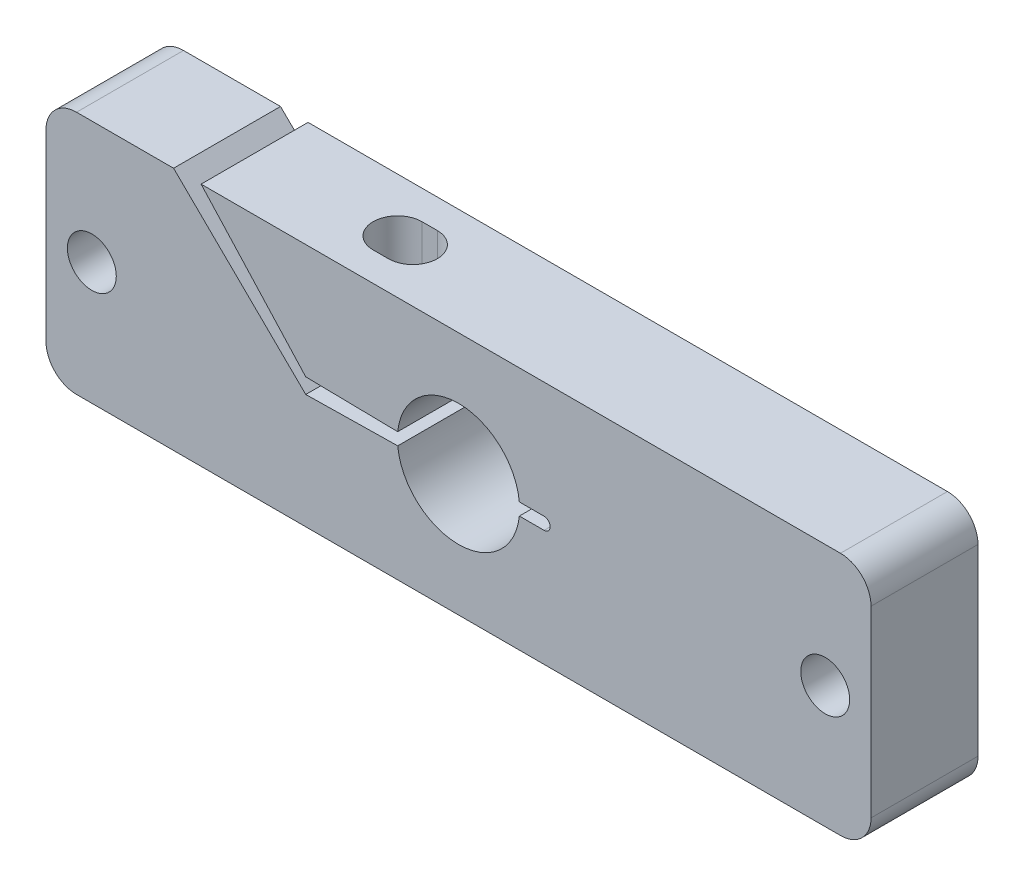
SolidWorks part; units mm, degrees
ref_plane "Front Plane" through (0, 0, 0) normal (0, 0, 1) x (1, 0, 0)
ref_plane "Top Plane" through (0, 0, 0) normal (0, 1, 0) x (1, 0, 0)
ref_plane "Right Plane" through (0, 0, 0) normal (1, 0, 0) x (0, 0, -1)
sketch "Sketch1" plane through (0, 0, 0) normal (0, 0, 1) x (1, 0, 0)
  line L0 (-43.3338, 0) -> (30.2546, 0) construction
  line L1 (-10, 0) -> (-19.1197, 9.4437) construction
  line L2 (-27, 8) -> (-18.6497, 8)
  line L3 (-27, 8) -> (-27, -8)
  line L4 (-27, -8) -> (27, -8)
  line L5 (27, 8) -> (27, -8)
  line L6 (-10, 0.5) -> (-3.9799, 0.4)
  line L7 (-10, 0.5) -> (-10, -0.5) construction
  line L8 (-10, -0.5) -> (-3.9799, -0.4)
  line L9 (6, 0.4) -> (6, -0.4)
  line L10 (-10, 0.5) -> (-16.8484, 8)
  line L11 (-10, -0.5) -> (-18.6497, 8)
  line L12 (3.9799, 0.4) -> (6, 0.4)
  line L13 (3.9799, -0.4) -> (6, -0.4)
  line L14 (-16.8484, 8) -> (27, 8)
  line L15 (0, 10.4655) -> (0, -11.9899) construction
  arc A0 (-3.9799, -0.4) -> (3.9799, -0.4) centre (0, 0) ccw
  arc A1 (3.9799, 0.4) -> (-3.9799, 0.4) centre (0, 0) ccw
  circle A2 centre (-24, 0) radius 2.2 construction
  circle A3 centre (-24, 0) radius 1.6
  circle A4 centre (24, 0) radius 1.6
  dimension "D1" = 8
  dimension "D2" = 4.4
  dimension "D4" = 3
  dimension "D5" = 48
  dimension "D7" = 2
  dimension "D16" = 3.2
  dimension "D3" = 8
  dimension "D6" = 0.8
  dimension "D8" = 46
  dimension "D9" = 6
  dimension "D10" = 1.5
  dimension "D11" = 1.6
  dimension "D14" = 0.8
  dimension "D15" = 1
extrude "Boss-Extrude1" add sketch "Sketch1" along normal blind 3.5 and the other way blind 3.5
sketch "Sketch3" plane through (0, -8, 0) normal (0, -1, 0) x (1, 0, 0)
  line L0 (-10, 3.5) -> (-3.9799, 3.5) construction
  line L1 (-27, 3.5) -> (27, 3.5) construction
  line L7 (-6.99, 2.7251) -> (-6.99, -2.5156) construction
  line L10 (27, -3.5) -> (27, 3.5) construction
  circle A0 centre (-6.99, 0) radius 2.2
  circle A1 centre (-6.99, 0) radius 1.6
  point P6 (-6.99, 3.5)
  dimension "D1" = 4.4
  dimension "D2" = 3.2
extrude "Cut-Extrude1" cut sketch "Sketch3" against normal up to next contours A1
extrude "Cut-Extrude2" cut sketch "Sketch3<3>" against normal blind 6
sketch "Sketch3<3>" plane through (0, -8, 0) normal (0, -1, 0) x (1, 0, 0) same geometry as "Sketch3"
sketch "Sketch4" plane through (0, 8, 0) normal (0, 1, 0) x (1, 0, 0)
  line L0 (-7.49, 0) -> (-6.49, 0) construction
  line L1 (-7.49, 1.6) -> (-6.49, 1.6)
  line L2 (-7.49, -1.6) -> (-6.49, -1.6)
  arc A0 (-7.49, 1.6) -> (-7.49, -1.6) centre (-7.49, 0) ccw
  arc A1 (-6.49, -1.6) -> (-6.49, 1.6) centre (-6.49, 0) ccw
  point P2 (-6.99, 0)
  dimension "D1" = 3.2
  dimension "D2" = 1
extrude "Cut-Extrude3" cut sketch "Sketch4" against normal up to next
fillet "Fillet1" radius 2 4 edges at (-27, -8, 0) (27, -8, 0) (27, 8, 0) (-27, 8, 0)
fillet "Fillet2" 2 edges at (6, 0.4, 0) (6, -0.4, 0) type full round first side face at (4.99, 0.4, 0) second side face at (4.99, -0.4, 0) middle face at (6, 0, 0)
